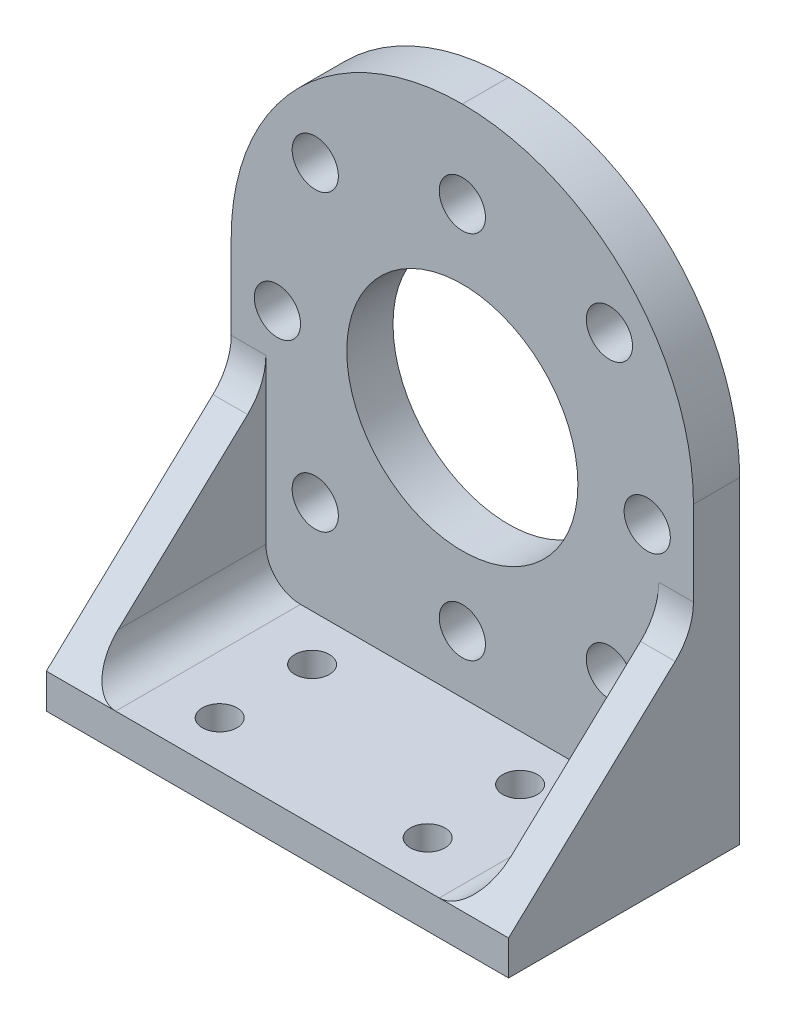
SolidWorks part; units mm, degrees
material "6061 合金"
ref_plane "前视基准面" through (0, 0, 0) normal (0, 0, 1) x (1, 0, 0)
ref_plane "上视基准面" through (0, 0, 0) normal (0, 1, 0) x (1, 0, 0)
ref_plane "右视基准面" through (0, 0, 0) normal (1, 0, 0) x (0, 0, -1)
sketch "草图1" plane through (0, 0, 0) normal (0, 1, 0) x (1, 0, 0)
  line L1 (-20, -10) -> (20, -10)
  line L2 (-20, -10) -> (-20, 10)
  line L3 (-20, 10) -> (20, 10)
  line L4 (20, -10) -> (20, 10)
  line L5 (-20, -10) -> (20, 10) construction
  line L6 (-20, 10) -> (20, -10) construction
  point P0 (0, 0)
  dimension "D1" = 40
  dimension "D2" = 20
extrude "凸台-拉伸1" add sketch "草图1" along normal blind 3
sketch "草图2" plane through (0, 3, 0) normal (0, 1, 0) x (1, 0, 0)
  line L0 (20, -10) -> (20, 10) construction
  line L1 (-20, 10) -> (20, 10)
  line L2 (-20, 10) -> (-20, 6)
  line L3 (-20, 6) -> (20, 6)
  line L4 (20, 10) -> (20, 6)
  dimension "D1" = 4
extrude "凸台-拉伸2" add sketch "草图2" along normal blind 44.5
sketch "草图3" plane through (0, 0, -6) normal (0, 0, 1) x (1, 0, 0)
  line L0 (0, 0) -> (0, 47.5) construction
  line L1 (-20, 0) -> (20, 0) construction
  line L2 (-20, 47.5) -> (20, 47.5) construction
  line L3 (0, 24) -> (12.7279, 36.7279) construction
  circle A0 centre (0, 24) radius 10
  circle A1 centre (0, 24) radius 18 construction
  circle A2 centre (12.7279, 36.7279) radius 2
  circle A3 centre (12.7279, 11.2721) radius 2
  circle A4 centre (-12.7279, 11.2721) radius 2
  circle A5 centre (-12.7279, 36.7279) radius 2
  point P20 (0, 24)
  dimension "D1" = 20
  dimension "D2" = 36
  dimension "D3" = 4
  dimension "D4" = 24
  dimension "D6" = 45
  dimension "D5" = 4
extrude "切除-拉伸1" cut sketch "草图3" against normal through all
fillet "圆角1" radius 20 2 edges at (20, 47.5, -8) (-20, 47.5, -8)
sketch "草图4" plane through (0, 3, 0) normal (0, 1, 0) x (1, 0, 0)
  line L0 (-20, -10) -> (20, -10) construction
  line L1 (-20, 6) -> (-17, 6)
  line L2 (-20, 6) -> (-20, -10)
  line L3 (-20, -10) -> (-17, -10)
  line L4 (-17, 6) -> (-17, -10)
  line L6 (20, 6) -> (17, 6)
  line L7 (20, 6) -> (20, -10)
  line L8 (20, -10) -> (17, -10)
  line L9 (17, 6) -> (17, -10)
  dimension "D1" = 3
  dimension "D2" = 3
extrude "凸台-拉伸3" add sketch "草图4" along normal blind 15
sketch "草图5" plane through (-20, 0, 0) normal (-1, 0, 0) x (0, 0, 1)
  line L0 (-6, 18) -> (10, 3)
  line L1 (10, 3) -> (10, 18)
  line L2 (10, 18) -> (-6, 18)
extrude "切除-拉伸2" cut sketch "草图5" against normal through all
fillet "圆角2" radius 5 2 edges at (18.5, 18, -6) (-18.5, 18, -6)
fillet "圆角3" radius 3 2 edges at (17, 3, 2) (-17, 3, 2)
sketch "草图6" plane through (0, 3, 0) normal (0, 1, 0) x (1, 0, 0)
  line L0 (0, 6) -> (0, -10) construction
  line L5 (-14, 6) -> (14, 6) construction
  line L6 (-14, -10) -> (14, -10) construction
  line L7 (-14, -2) -> (14, -2) construction
  line L8 (-14, 6) -> (-14, -10) construction
  line L9 (14, -10) -> (14, 6) construction
  line L11 (-9, -6) -> (9, -6) construction
  line L12 (-9, -6) -> (-9, 2) construction
  line L13 (-9, 2) -> (9, 2) construction
  line L14 (9, -6) -> (9, 2) construction
  line L15 (-9, -6) -> (9, 2) construction
  line L16 (-9, 2) -> (9, -6) construction
  circle A0 centre (-9, 2) radius 1.5
  circle A1 centre (9, 2) radius 1.5
  circle A2 centre (9, -6) radius 1.5
  circle A3 centre (-9, -6) radius 1.5
  point P12 (0, -2)
  dimension "D3" = 3
  dimension "D1" = 18
  dimension "D2" = 8
extrude "切除-拉伸3" cut sketch "草图6" against normal blind 3
sketch "草图7" plane through (0, 0, -6) normal (0, 0, 1) x (1, 0, 0)
  circle A0 centre (0, 24) radius 16 construction
  circle A1 centre (0, 40) radius 2
  circle A2 centre (-16, 24) radius 2
  circle A3 centre (0, 8) radius 2
  circle A4 centre (16, 24) radius 2
  point P14 (0, 24)
  dimension "D1" = 32
  dimension "D2" = 4
  dimension "D3" = 4
extrude "切除-拉伸4" cut sketch "草图7" against normal through all
